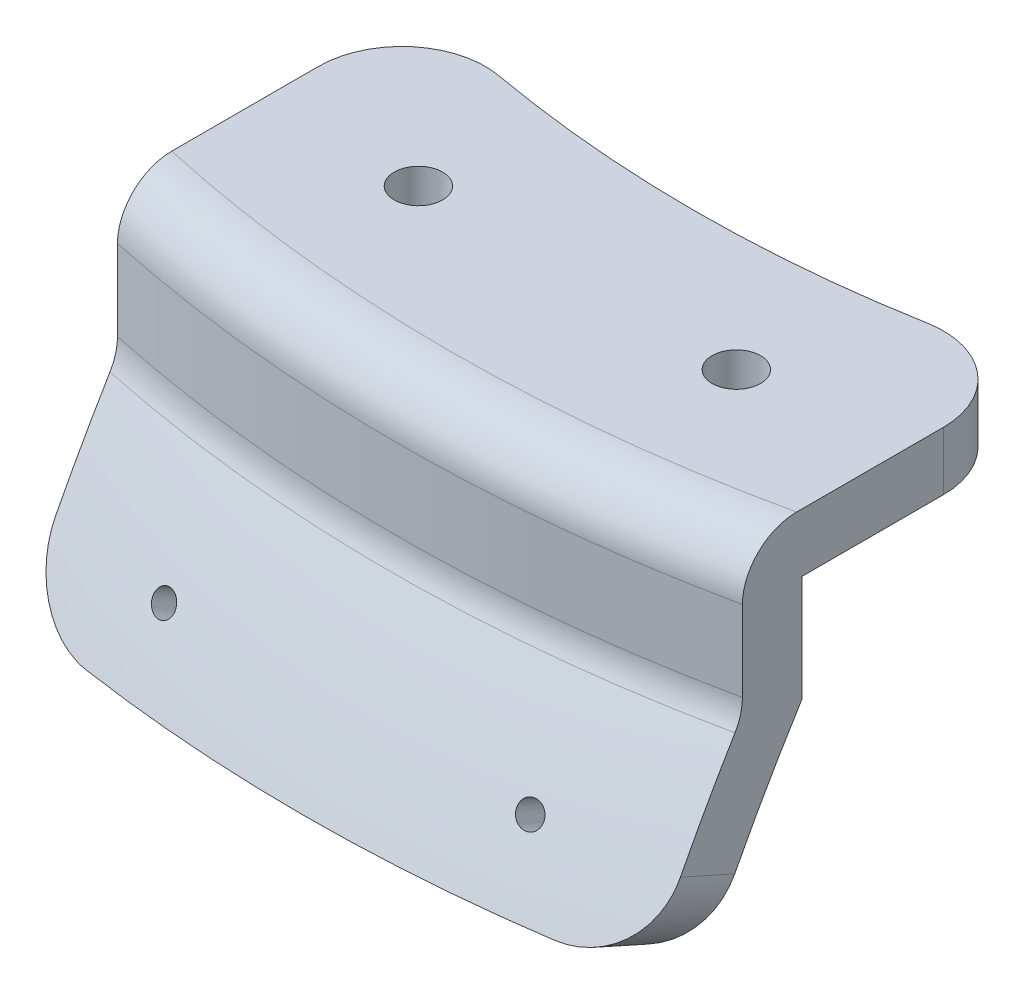
SolidWorks part; units mm, degrees
material "Polyether Polyol"
ref_plane "Front Plane" through (0, 0, 0) normal (0, 0, 1) x (1, 0, 0)
ref_plane "Top Plane" through (0, 0, 0) normal (0, 1, 0) x (1, 0, 0)
ref_plane "Right Plane" through (0, 0, 0) normal (1, 0, 0) x (0, 0, -1)
sketch "Sketch2" plane through (0, 0, 0) normal (1, 0, 0) x (0, 0, -1)
  line L0 (-173.2735, 210.7637) -> (-173.2735, 198.0637) construction
  line L1 (-191.5618, 178.4538) -> (-185.1824, 175.572) construction
  line L2 (-180.2735, 217.7637) -> (-180.2735, 200.0193) construction
  line L3 (-180.2735, 217.7637) -> (-144.6985, 217.7637) construction
  line L4 (-144.6985, 217.7637) -> (-144.6985, 210.7637) construction
  line L5 (-144.6985, 210.7637) -> (-173.2735, 210.7637) construction
  line L12 (0, 91.9198) -> (0, 210.7637) construction
  line L13 (-173.2735, 210.7637) -> (-173.2735, 198.0637)
  line L14 (-191.5618, 178.4538) -> (-185.1824, 175.572)
  line L15 (-180.2735, 217.7637) -> (-180.2735, 200.0193)
  line L16 (-180.2735, 217.7637) -> (-144.6985, 217.7637)
  line L17 (-144.6985, 217.7637) -> (-144.6985, 210.7637)
  line L18 (-144.6985, 210.7637) -> (-173.2735, 210.7637)
  arc A0 (-173.2735, 198.0637) -> (-185.1824, 175.572) centre (0, 91.9198) ccw construction
  arc A1 (-180.2735, 200.0193) -> (-191.5618, 178.4538) centre (0, 91.9198) ccw construction
  arc A4 (-173.2735, 198.0637) -> (-185.1824, 175.572) centre (0, 91.9198) ccw
  arc A5 (-180.2735, 200.0193) -> (-191.5618, 178.4538) centre (0, 91.9198) ccw
revolve "Revolve1" add sketch "Sketch2" angle 30 mid plane about L12
fillet "Fillet1" radius 6.35 2 edges at (0, 200.0193, 180.2735) (0, 217.7637, 180.2735)
sketch "Sketch3" plane through (0, 217.7637, 0) normal (0, -1, 0) x (1, 0, 0)
  circle A2 centre (-19.05, 158.6742) radius 3.5719 construction
  circle A3 centre (19.05, 158.6742) radius 3.5719 construction
  circle A4 centre (19.05, 158.6742) radius 2.9
  circle A5 centre (-19.05, 158.6742) radius 2.9
  dimension "D1" = 5.8
extrude "Cut-Extrude1" cut sketch "Sketch3" along normal through all contours A4 | A5 region at (19.05, 217.7637, 158.6742) region at (-19.05, 217.7637, 158.6742)
sketch "Sketch4" plane through (0, 217.7637, 0) normal (0, 1, 0) x (1, 0, 0)
  line L0 (37.4507, -139.768) -> (45.0147, -167.9972) construction
  line L1 (37.4507, -139.768) -> (-37.4507, -139.768)
  line L2 (37.4507, -139.768) -> (37.4507, -191.5618)
  line L3 (37.4507, -191.5618) -> (-37.4507, -191.5618)
  line L4 (-37.4507, -139.768) -> (-37.4507, -191.5618)
  line L5 (-37.4507, -139.768) -> (-45.0147, -167.9972) construction
  arc A0 (-37.4507, -139.768) -> (37.4507, -139.768) centre (0, 0) ccw construction
  arc A1 (-49.5798, -185.0345) -> (49.5798, -185.0345) centre (0, 0) ccw construction
extrude "Cut-Extrude2" cut sketch "Sketch4" against normal through all flip side to cut
fillet "Fillet2" radius 10 4 edges at (-37.4507, 214.2637, 139.768) (37.4507, 214.2637, 139.768)
sketch "Sketch5" plane through (0, 0, 0) normal (-1, 0, 0) x (0, 0, 1)
  line L0 (0, 91.9198) -> (181.0525, 184.1706) construction
  line L2 (0, -200000) -> (0, 218797.9879) construction
  arc A0 (185.1824, 175.572) -> (173.2735, 198.0637) centre (0, 91.9198) ccw construction
  dimension "D1" = 63
ref_plane "Plane1" through (0, 72.9744, -37.1823) normal (0, 0.891, -0.454) x (0, 0.454, 0.891)
sketch "Sketch6" plane through (0, 72.9744, -37.1823) normal (0, 0.891, -0.454) x (0, 0.454, 0.891)
  line L0 (217.7243, 19.0484) -> (275.7942, 24.1289) construction
  line L2 (217.7243, 19.0484) -> (275.7942, 24.1289)
  line L3 (217.7243, 19.0484) -> (217.5936, 20.5427)
  line L4 (275.7942, 24.1289) -> (275.6635, 25.6232)
  line L5 (217.5936, 20.5427) -> (275.6635, 25.6232)
  line L6 (41.7307, 0) -> (244.9307, 0) construction
  ellipse E0 centre (89.9191, 0) end of major axis (89.9191, 144.6985) minor radius 128.9273 construction
  dimension "D1" = 5
  dimension "D2" = 1.5
revolve "Cut-Revolve1" cut sketch "Sketch6" angle 360 about L0
mirror "Mirror1" about plane through (0, 0, 0) normal (1, 0, 0) of "Cut-Revolve1"
